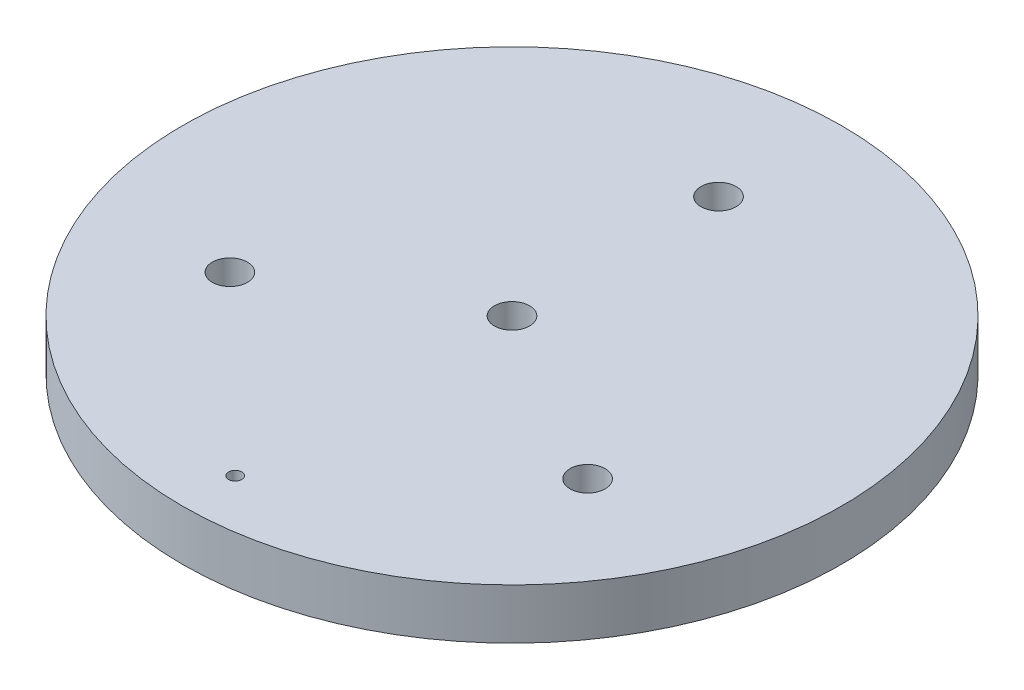
SolidWorks part; units mm, degrees
material "Zoltek Panex 33"
ref_plane "Ebene vorne" through (0, 0, 0) normal (0, 0, 1) x (1, 0, 0)
ref_plane "Ebene oben" through (0, 0, 0) normal (0, 1, 0) x (1, 0, 0)
ref_plane "Ebene rechts" through (0, 0, 0) normal (1, 0, 0) x (0, 0, -1)
sketch "Sketch1" plane through (0, 0, 0) normal (0, 1, 0) x (1, 0, 0)
  circle A0 centre (0, 0) radius 75
  dimension "D1" = 150
extrude "Boss-Extrude1" add sketch "Sketch1" along normal blind 11.482
sketch "Sketch2" plane through (0, 11.482, 0) normal (0, 1, 0) x (1, 0, 0)
  line L0 (0, 0) -> (0, 66.4755) construction
  circle A0 centre (0, 47) radius 4
  dimension "D1" = 8
  dimension "D2" = 47
extrude "Cut-Extrude1" cut sketch "Sketch2" against normal through all
ref_axis "Axis1" through (0, 33.6, 0) along (0, -1, 0)
pattern_circular "CirPattern1" count 3 over 360 about axis through (0, 33.6, 0) along (0, -1, 0) of "Cut-Extrude1"
sketch "Sketch3" plane through (0, 11.482, 0) normal (0, 1, 0) x (1, 0, 0)
  circle A0 centre (0, -63) radius 1.5
  dimension "D1" = 3
  dimension "D2" = 63
extrude "Cut-Extrude2" cut sketch "Sketch3" against normal through all
sketch "Sketch4" plane through (0, 11.482, 0) normal (0, 1, 0) x (1, 0, 0)
  circle A0 centre (0, 0) radius 4
  dimension "D1" = 8
extrude "Cut-Extrude3" cut sketch "Sketch4" against normal through all
equation "\"d_i_tube\"= 150mm'Inner Rocket Body Composite Tube Diameter"
equation "\"t_tube\"= 1.182mm'Thickness of Rocket Body Composite Tube"
equation "\"l_upper_body_tube\"= 1190mm'Upper Rocket Body Composite Tube length"
equation "\"l_lower_body_tube\"= 796mm'Lower Rocket Body Composite Tube Length"
equation "\"d_a_NC\"= 154mm'Outer Diameter of Nosecone base"
equation "\"d_i_phenolic_tube\"= 152.3mm'Inner Phenolic Tube Diameter"
equation "\"t_phenolic_tube\"= 2mm'Thickness of Phenolic Body Tube"
equation "\"l_fin_cut\"= 220mm'Length of fin on Motor Retainer"
equation "\"t_SW-Panel\"= 11.482mm'Thickness of Sandwich-Panel"
equation "\"l_motor_tube\"=650mm'Length of phenolic motor tube"
equation "\"d_i_motor_tube\"=99.06mm'Inner diameter of phenolic motor tube"
equation "\"t_motor_tube\"=1.58mm'Thicknes of phenolic motor tube"
equation "\"l_cut_fin_centering\"=13mm'Length of cut for fin alignement on fin centering rings"
equation "\"l_M3_threaded_rods\"=220mm'Length of M3 threaded rods for thrust plate force transmission"
equation "\"D1@Boss-Extrude1\"=\"t_SW-Panel\""
equation "\"D1@Sketch1\"=\"d_i_tube\""
